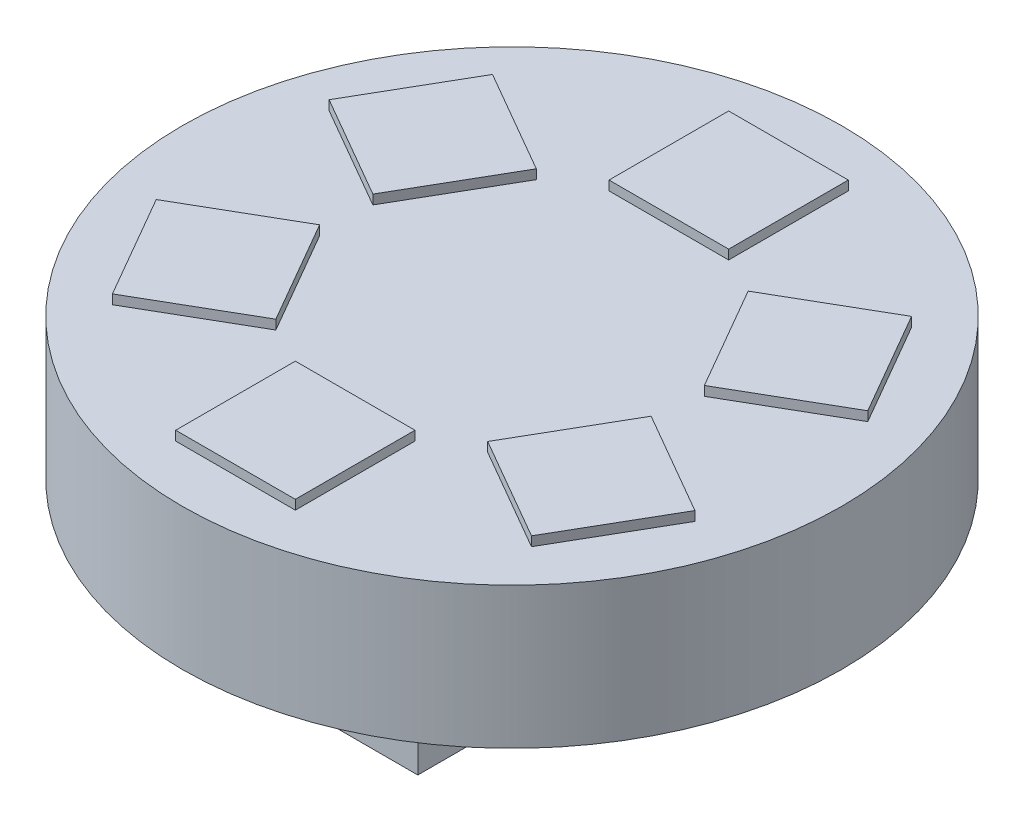
SolidWorks part; units mm, degrees
ref_plane "Front Plane" through (0, 0, 0) normal (0, 0, 1) x (1, 0, 0)
ref_plane "Top Plane" through (0, 0, 0) normal (0, 1, 0) x (1, 0, 0)
ref_plane "Right Plane" through (0, 0, 0) normal (1, 0, 0) x (0, 0, -1)
sketch "Sketch1" plane through (0, 0, 0) normal (0, 1, 0) x (1, 0, 0)
  line L1 (-1.22, 2.22) -> (1.22, 2.22)
  line L2 (-1.22, 2.22) -> (-1.22, -2.22)
  line L3 (-1.22, -2.22) -> (1.22, -2.22)
  line L4 (1.22, 2.22) -> (1.22, -2.22)
  line L5 (-1.22, 2.22) -> (1.22, -2.22) construction
  line L6 (-1.22, -2.22) -> (1.22, 2.22) construction
  circle A0 centre (0, 0) radius 3.5
  dimension "D1" = 7
  dimension "D2" = 4.44
  dimension "D3" = 2.44
extrude "Boss-Extrude1" add sketch "Sketch1" along normal blind 1.5 contours L4 L1 L2 L3 | A0 L1 L4 L3 L2 region at (0, 0, 0) region at (-3.401, 0, 0)
extrude "Boss-Extrude2" add sketch "Sketch1<3>" against normal blind 1 contours L4 L1 L2 L3 region at (0, 0, 0)
sketch "Sketch1<3>" plane through (0, 0, 0) normal (0, 1, 0) x (1, 0, 0) same geometry as "Sketch1"
sketch "Sketch2" plane through (0, 1.5, 0) normal (0, 1, 0) x (1, 0, 0)
  line L0 (0, 0) -> (0, 3.5) construction
  line L1 (-0.635, 2.935) -> (0.635, 2.935)
  line L2 (-0.635, 2.935) -> (-0.635, 1.665)
  line L3 (-0.635, 1.665) -> (0.635, 1.665)
  line L4 (0.635, 2.935) -> (0.635, 1.665)
  line L5 (-0.635, 2.935) -> (0.635, 1.665) construction
  line L6 (-0.635, 1.665) -> (0.635, 2.935) construction
  line L7 (2.2243, 2.0174) -> (1.1244, 1.3824)
  line L8 (2.2243, 2.0174) -> (2.8593, 0.9176)
  line L9 (2.8593, 0.9176) -> (1.7594, 0.2826)
  line L10 (1.1244, 1.3824) -> (1.7594, 0.2826)
  line L11 (2.8593, -0.9176) -> (1.7594, -0.2826)
  line L12 (2.8593, -0.9176) -> (2.2243, -2.0174)
  line L13 (2.2243, -2.0174) -> (1.1244, -1.3824)
  line L14 (1.7594, -0.2826) -> (1.1244, -1.3824)
  line L15 (0.635, -2.935) -> (0.635, -1.665)
  line L16 (0.635, -2.935) -> (-0.635, -2.935)
  line L17 (-0.635, -2.935) -> (-0.635, -1.665)
  line L18 (0.635, -1.665) -> (-0.635, -1.665)
  line L19 (-2.2243, -2.0174) -> (-1.1244, -1.3824)
  line L20 (-2.2243, -2.0174) -> (-2.8593, -0.9176)
  line L21 (-2.8593, -0.9176) -> (-1.7594, -0.2826)
  line L22 (-1.1244, -1.3824) -> (-1.7594, -0.2826)
  line L23 (-2.8593, 0.9176) -> (-1.7594, 0.2826)
  line L24 (-2.8593, 0.9176) -> (-2.2243, 2.0174)
  line L25 (-2.2243, 2.0174) -> (-1.1244, 1.3824)
  line L26 (-1.7594, 0.2826) -> (-1.1244, 1.3824)
  circle A0 centre (0, 0) radius 3.5 construction
  point P0 (0, 2.3)
  point P7 (0, 0)
  point P9 (0, 0)
  point P34 (0, 0)
  dimension "D1" = 1.27
  dimension "D2" = 1.27
  dimension "D4" = 2.3
  dimension "D3" = 6
extrude "Boss-Extrude3" add sketch "Sketch2" along normal blind 0.1 contours L4 L1 L2 L3 | L7 L10 L9 L8 | L11 L14 L13 L12 | L15 L18 L17 L16 | L19 L22 L21 L20 | L23 L26 L25 L24 region at (0, 1.5, -2.3) region at (1.9919, 1.5, -1.15) region at (1.9919, 1.5, 1.15) region at (0, 1.5, 2.3) region at (-1.9919, 1.5, 1.15)
